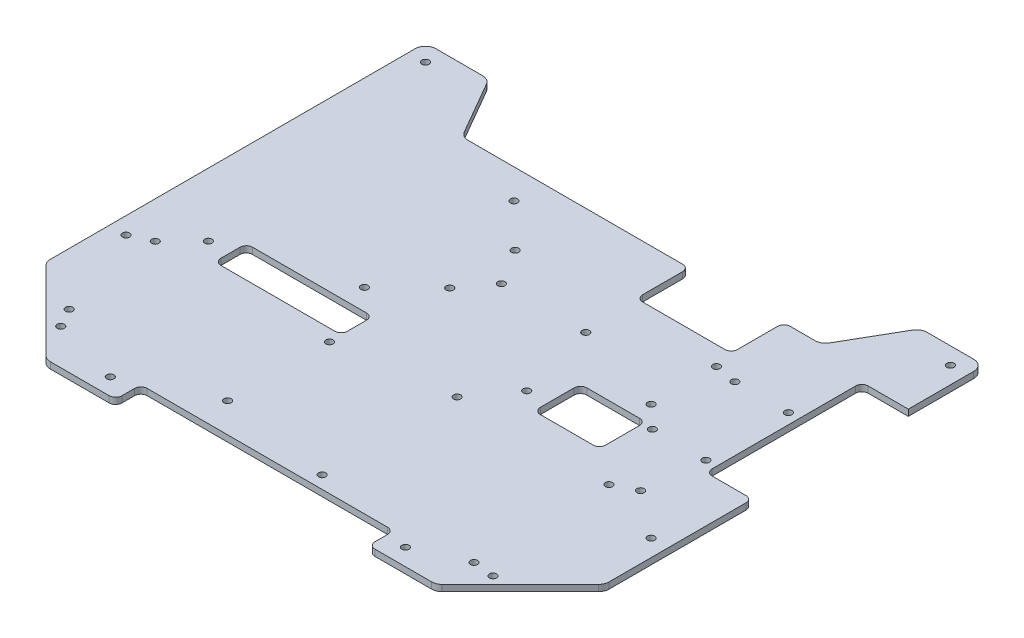
SolidWorks part; units mm, degrees
material "Acier non allié"
ref_plane "Front" through (0, 0, 0) normal (0, 0, 1) x (1, 0, 0)
ref_plane "Top" through (0, 0, 0) normal (0, 1, 0) x (1, 0, 0)
ref_plane "Right" through (0, 0, 0) normal (1, 0, 0) x (0, 0, -1)
sketch "Esquisse1" plane through (0, 0, 0) normal (0, 1, 0) x (1, 0, 0)
  line L0 (0, 0) -> (0, 190) construction
  line L1 (-92.5, 0) -> (92.5, 0)
  line L2 (92.5, 0) -> (132.5, 40)
  line L3 (132.5, 40) -> (132.5, 220)
  line L4 (132.5, 220) -> (102.5, 220)
  line L5 (102.5, 220) -> (85.1795, 190)
  line L6 (85.1795, 190) -> (-85.1795, 190)
  line L7 (-102.5, 220) -> (-85.1795, 190)
  line L8 (-132.5, 220) -> (-102.5, 220)
  line L9 (-132.5, 40) -> (-132.5, 220)
  line L10 (-92.5, 0) -> (-132.5, 40)
  dimension "D1" = 132.5
  dimension "D2" = 220
  dimension "D3" = 60
  dimension "D4" = 30
  dimension "D5" = 40
  dimension "D6" = 40
  dimension "D7" = 30
extrude "Boss.-Extru.1" add sketch "Esquisse1" along normal blind 3
fillet "Congé1" radius 5 10 edges at (92.5, 1.5, 0) (132.5, 1.5, -40) (132.5, 1.5, -220) (102.5, 1.5, -220) (85.1795, 1.5, -190) (-85.1795, 1.5, -190) (-102.5, 1.5, -220) (-132.5, 1.5, -220) (-92.5, 1.5, 0) (-132.5, 1.5, -40)
sketch "Esquisse2" plane through (0, 3, 0) normal (0, 1, 0) x (1, 0, 0)
  line L0 (0, 0) -> (0, 294.1173) construction
  line L2 (-90.4289, 0) -> (90.4289, 0) construction
  circle A0 centre (70, 8) radius 1
  circle A1 centre (124.5, 70) radius 1
  circle A2 centre (124.5, 212) radius 1
  circle A3 centre (-124.5, 212) radius 1
  circle A4 centre (-124.5, 70) radius 1
  circle A5 centre (-70, 8) radius 1
  dimension "D2" = 2
  dimension "D6" = 2
  dimension "D9" = 2
  dimension "D1" = 70
  dimension "D3" = 8
  dimension "D4" = 124.5
  dimension "D5" = 70
  dimension "D7" = 124.5
  dimension "D8" = 212
extrude "Enlèv. mat.-Extru.1" cut sketch "Esquisse2" against normal blind 3
hole_wizard "Dégagement M31" positions "Esquisse3" profile "Esquisse4" hole size "M3" standard "ISO" end condition through all
sketch "Esquisse3" plane through (0, 3, 0) normal (0, 1, 0) x (1, 0, 0)
  point P0 (70, 8)
  point P3 (-70, 8)
  point P6 (-124.5, 70)
  point P9 (-124.5, 212)
  point P12 (124.5, 212)
  point P15 (124.5, 70)
sketch "Esquisse4" plane through (70, 3, -8) normal (1, 0, 0) x (0, 0, 1)
  line L0 (0, 0) -> (0, 3)
  line L1 (0, 3) -> (1.7, 3)
  line L2 (1.7, 3) -> (1.7, 0)
  line L5 (1.7, 0) -> (0, 0)
  line L11 (0, -6.35) -> (0, 107.95) construction
  dimension "Diamètre du perçage jusqu'au prochain" = 3.4
  dimension "Profondeur du perçage jusqu'au prochain" = 3
sketch "Esquisse5" plane through (0, 3, 0) normal (0, 1, 0) x (1, 0, 0)
  line L0 (82.2927, 190) -> (-82.2927, 190) construction
  line L1 (67.5, 190) -> (22.5, 190)
  line L2 (67.5, 190) -> (67.5, 165)
  line L3 (67.5, 165) -> (22.5, 165)
  line L4 (22.5, 190) -> (22.5, 165)
  line L5 (132.5, 42.0711) -> (132.5, 215) construction
  line L6 (132.5, 184) -> (110.5, 184)
  line L7 (132.5, 184) -> (132.5, 110)
  line L8 (132.5, 110) -> (110.5, 110)
  line L9 (110.5, 184) -> (110.5, 110)
  line L10 (127.5, 220) -> (105.3868, 220) construction
  dimension "D1" = 25
  dimension "D2" = 65
  dimension "D3" = 110
  dimension "D4" = 36
  dimension "D5" = 110
  dimension "D6" = 22
extrude "Enlèv. mat.-Extru.2" cut sketch "Esquisse5" against normal through all
fillet "Congé2" radius 3 7 edges at (132.5, 1.5, -110) (110.5, 1.5, -110) (110.5, 1.5, -184) (67.5, 1.5, -190) (67.5, 1.5, -165) (22.5, 1.5, -165) (22.5, 1.5, -190)
sketch "Esquisse6" plane through (0, 3, 0) normal (0, 1, 0) x (1, 0, 0)
  line L0 (110.5, 140.5) -> (-167.6757, 140.5) construction
  line L1 (110.5, 181) -> (110.5, 113) construction
  line L2 (-90.4289, 0) -> (90.4289, 0) construction
  line L3 (110.5, 181) -> (110.5, 113) construction
  circle A0 centre (69.5, 156) radius 1
  circle A1 centre (-26, 156) radius 1
  circle A2 centre (-46.5, 176) radius 1
  circle A3 centre (69.5, 125) radius 1
  circle A4 centre (-26, 125) radius 1
  circle A5 centre (-46.5, 105) radius 1
  dimension "D4" = 2
  dimension "D6" = 2
  dimension "D10" = 2
  dimension "D1" = 140.5
  dimension "D2" = 41
  dimension "D3" = 15.5
  dimension "D5" = 136.5
  dimension "D7" = 15.5
  dimension "D8" = 35.5
  dimension "D9" = 157
extrude "Enlèv. mat.-Extru.3" cut sketch "Esquisse6" against normal through all
hole_wizard "Dégagement M32" positions "Esquisse7" profile "Esquisse8" hole size "M3" standard "ISO"
sketch "Esquisse7" plane through (0, 3, 0) normal (0, 1, 0) x (1, 0, 0)
  point P0 (-46.5, 105)
  point P3 (-26, 125)
  point P6 (-26, 156)
  point P9 (-46.5, 176)
  point P12 (69.5, 156)
  point P15 (69.5, 125)
sketch "Esquisse8" plane through (-46.5, 3, -105) normal (1, 0, 0) x (0, 0, 1)
  line L0 (0, 0) -> (0, 11.0215)
  line L1 (0, 11.0215) -> (1.7, 10)
  line L2 (1.7, 10) -> (1.7, 0)
  line L5 (1.7, 0) -> (0, 0)
  line L10 (0, 11.0215) -> (-1.7, 10) construction
  line L11 (0, -6.35) -> (0, 107.95) construction
  dimension "Diamètre du perçage" = 3.4
  dimension "Profondeur du perçage" = 10
  dimension "Angle de pointe" = 118
sketch "Esquisse9" plane through (0, 3, 0) normal (0, 1, 0) x (1, 0, 0)
  line L0 (132.5, 42.0711) -> (132.5, 107) construction
  line L1 (-90.4289, 0) -> (90.4289, 0) construction
  line L2 (-107.5, 26) -> (-32.37, 26) construction
  line L7 (20.5, 18) -> (20.5, 82) construction
  line L8 (25.5, 165) -> (64.5, 165) construction
  line L9 (24.5, 139) -> (-15.5, 139) construction
  line L10 (110.5, 181) -> (110.5, 113) construction
  line L11 (113.5, 110) -> (129.5, 110) construction
  line L13 (-32.37, 26) -> (-32.37, 74.3362) construction
  line L14 (-32.37, 74.3362) -> (-115, 74.3362) construction
  line L15 (-132.5, 215) -> (-132.5, 42.0711) construction
  circle A0 centre (105.5, 115) radius 1
  circle A3 centre (105.5, 154.12) radius 1
  circle A10 centre (20.5, 82) radius 1
  circle A11 centre (92.5, 82) radius 1
  circle A12 centre (20.5, 18) radius 1
  circle A13 centre (92.5, 18) radius 1
  circle A14 centre (-15.5, 139) radius 1
  circle A15 centre (24.5, 139) radius 1
  circle A16 centre (34.5, 101) radius 1
  circle A17 centre (80.1, 115) radius 1
  circle A18 centre (80.1, 154.12) radius 1
  circle A19 centre (-107.5, 26) radius 1.5
  circle A21 centre (-32.37, 26) radius 1.5
  circle A22 centre (-32.37, 74.3362) radius 1.5
  circle A23 centre (-115, 74.3362) radius 1.5
  dimension "D2" = 2
  dimension "D4" = 2
  dimension "D21" = 2
  dimension "D22" = 2
  dimension "D23" = 2
  dimension "D24" = 2
  dimension "D32" = 2
  dimension "D33" = 2
  dimension "D34" = 2
  dimension "D11" = 2
  dimension "D12" = 2
  dimension "D17" = 3
  dimension "D18" = 3
  dimension "D19" = 3
  dimension "D36" = 3
  dimension "D5" = 27
  dimension "25" = 27
  dimension "D10" = 39.12
  dimension "D25" = 72
  dimension "D26" = 72
  dimension "D27" = 64
  dimension "D28" = 64
  dimension "D30" = 18
  dimension "D31" = 18
  dimension "D37" = 40
  dimension "D39" = 10
  dimension "D7" = 5
  dimension "D8" = 25.4
  dimension "D9" = 25.4
  dimension "D40" = 39.12
  dimension "D38" = 76
  dimension "D6" = 38
  dimension "D35" = 26
  dimension "D14" = 40
  dimension "D13" = 75.13
  dimension "D15" = 82.63
  dimension "D16" = 48.3362
  dimension "D20" = 26
  dimension "D29" = 25
extrude "Enlèv. mat.-Extru.4" cut sketch "Esquisse9" against normal through all
hole_wizard "Dégagement M33" positions "Esquisse10" profile "Esquisse11" hole size "M3" standard "ISO"
sketch "Esquisse10" plane through (0, 3, 0) normal (0, 1, 0) x (1, 0, 0)
  point P3 (105.5, 115)
  point P9 (105.5, 154.12)
  point P14 (80.1, 154.12)
  point P17 (80.1, 115)
sketch "Esquisse11" plane through (105.5, 3, -115) normal (1, 0, 0) x (0, 0, 1)
  line L0 (0, 0) -> (0, 11.0215)
  line L1 (0, 11.0215) -> (1.7, 10)
  line L2 (1.7, 10) -> (1.7, 0)
  line L5 (1.7, 0) -> (0, 0)
  line L10 (0, 11.0215) -> (-1.7, 10) construction
  line L11 (0, -6.35) -> (0, 107.95) construction
  dimension "Diamètre du perçage" = 3.4
  dimension "Profondeur du perçage" = 10
  dimension "Angle de pointe" = 118
sketch "Esquisse12" plane through (0, 3, 0) normal (0, 1, 0) x (1, 0, 0)
  line L2 (-90.4289, 0) -> (90.4289, 0) construction
  line L3 (102.5, 17) -> (-102.5, 17) construction
  line L4 (102.5, 17) -> (102.5, 87) construction
  line L5 (102.5, 87) -> (-102.5, 87) construction
  line L6 (-102.5, 17) -> (-102.5, 87) construction
  line L7 (132.5, 42.0711) -> (132.5, 107) construction
  circle A4 centre (-102.5, 87) radius 1
  circle A5 centre (102.5, 87) radius 1
  circle A6 centre (102.5, 17) radius 1
  circle A7 centre (-102.5, 17) radius 1
  point P6 (102.5, 52)
  dimension "D5" = 2
  dimension "D6" = 2
  dimension "D7" = 2
  dimension "D8" = 2
  dimension "D1" = 70
  dimension "D2" = 205
  dimension "D3" = 17
  dimension "D4" = 30
extrude "Enlèv. mat.-Extru.5" cut sketch "Esquisse12" against normal through all and the other way through all
hole_wizard "Dégagement M34" positions "Esquisse13" profile "Esquisse14" hole size "M3" standard "ISO"
sketch "Esquisse13" plane through (0, 3, 0) normal (0, 1, 0) x (1, 0, 0)
  point P16 (20.5, 18)
  point P19 (92.5, 18)
  point P22 (20.5, 82)
  point P25 (92.5, 82)
  point P29 (34.5, 101)
  point P32 (24.5, 139)
  point P35 (-15.5, 139)
  point P38 (-115, 74.3362)
  point P41 (-32.37, 74.3362)
  point P44 (-107.5, 26)
  point P47 (-32.37, 26)
sketch "Esquisse14" plane through (20.5, 3, -18) normal (1, 0, 0) x (0, 0, 1)
  line L0 (0, 0) -> (0, 11.0215)
  line L1 (0, 11.0215) -> (1.7, 10)
  line L2 (1.7, 10) -> (1.7, 0)
  line L5 (1.7, 0) -> (0, 0)
  line L10 (0, 11.0215) -> (-1.7, 10) construction
  line L11 (0, -6.35) -> (0, 107.95) construction
  dimension "Diamètre du perçage" = 3.4
  dimension "Profondeur du perçage" = 10
  dimension "Angle de pointe" = 118
hole_wizard "Dégagement M35" positions "Esquisse15" profile "Esquisse16" hole size "M3" standard "ISO"
sketch "Esquisse15" plane through (0, 3, 0) normal (0, 1, 0) x (1, 0, 0)
  point P0 (-102.5, 17)
  point P3 (-102.5, 87)
  point P6 (102.5, 87)
  point P9 (102.5, 17)
sketch "Esquisse16" plane through (-102.5, 3, -17) normal (1, 0, 0) x (0, 0, 1)
  line L0 (0, 0) -> (0, 11.0215)
  line L1 (0, 11.0215) -> (1.7, 10)
  line L2 (1.7, 10) -> (1.7, 0)
  line L5 (1.7, 0) -> (0, 0)
  line L10 (0, 11.0215) -> (-1.7, 10) construction
  line L11 (0, -6.35) -> (0, 107.95) construction
  dimension "Diamètre du perçage" = 3.4
  dimension "Profondeur du perçage" = 10
  dimension "Angle de pointe" = 118
sketch "Esquisse17" plane through (0, 3, 0) normal (0, 1, 0) x (1, 0, 0)
  line L0 (-90.4289, 0) -> (90.4289, 0) construction
  line L1 (-92.5, 95) -> (-32.5, 95)
  line L2 (-92.5, 95) -> (-92.5, 80)
  line L3 (-92.5, 80) -> (-32.5, 80)
  line L4 (-32.5, 95) -> (-32.5, 80)
  line L5 (-132.5, 215) -> (-132.5, 42.0711) construction
  line L6 (132.5, 42.0711) -> (132.5, 107) construction
  line L7 (44.5, 116.5) -> (75.5, 116.5)
  line L8 (44.5, 116.5) -> (44.5, 94.5)
  line L9 (44.5, 94.5) -> (75.5, 94.5)
  line L10 (75.5, 116.5) -> (75.5, 94.5)
  line L11 (82.2927, 190) -> (70.5, 190) construction
  line L13 (-59.5, 12) -> (60.5, 12)
  line L14 (-59.5, 12) -> (-59.5, 0)
  line L15 (-59.5, 0) -> (60.5, 0)
  line L16 (60.5, 12) -> (60.5, 0)
  dimension "D1" = 60
  dimension "D2" = 15
  dimension "D3" = 80
  dimension "D4" = 40
  dimension "D5" = 31
  dimension "D6" = 22
  dimension "D7" = 57
  dimension "D8" = 73.5
  dimension "D9" = 12
  dimension "D11" = 120
  dimension "D12" = 72
extrude "Enlèv. mat.-Extru.6" cut sketch "Esquisse17" against normal up to surface (3 mm away) up to face at (-102.5, 0, -15.3)
fillet "Congé3" radius 3 12 edges at (60.5, 1.5, 0) (60.5, 1.5, -12) (-59.5, 1.5, -12) (-59.5, 1.5, 0) (44.5, 1.5, -116.5) (75.5, 1.5, -116.5) (75.5, 1.5, -94.5) (44.5, 1.5, -94.5) (-92.5, 1.5, -80) (-32.5, 1.5, -80) (-32.5, 1.5, -95) (-92.5, 1.5, -95)
equation "\"WIDTH\"= 300mm'Total width of the robot"
equation "\"LENGTH\"= 220mm'Total length of the robot"
equation "\"CUT_DEPTH\"= 45mm'Depth of the cut on the edges of the plate"
equation "\"Plate_th\"= 3mm'Thickness of the plate"
equation "\"D1\"= \"Plate_th\""
equation "\"D5@Esquisse9\"=\"25@Esquisse9\""
